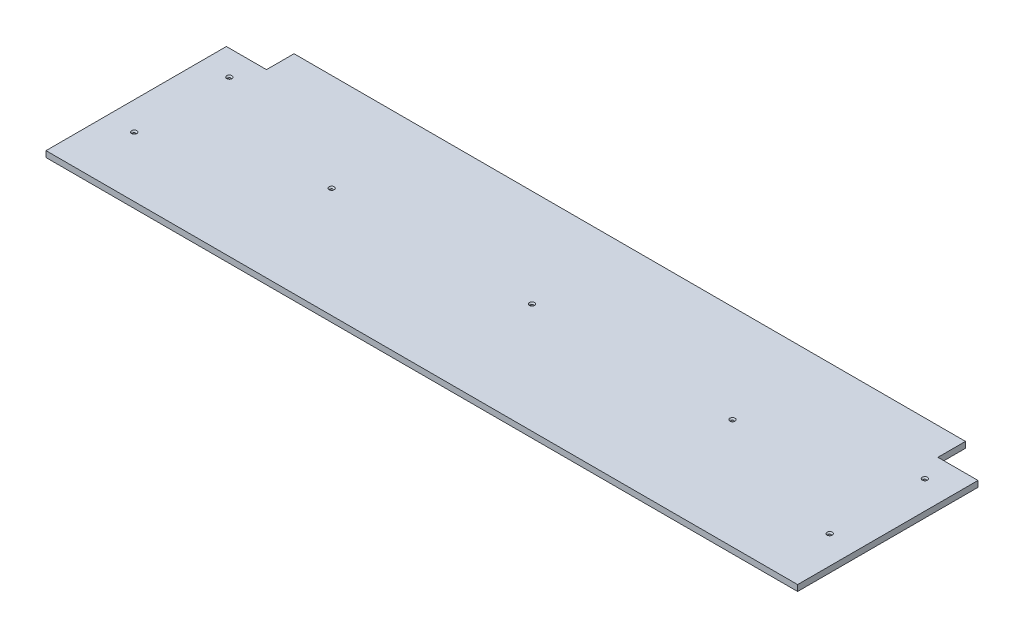
SolidWorks part; units mm, degrees
material "Balsa"
ref_plane "Front Plane" through (0, 0, 0) normal (0, 0, 1) x (1, 0, 0)
ref_plane "Top Plane" through (0, 0, 0) normal (0, 1, 0) x (1, 0, 0)
ref_plane "Right Plane" through (0, 0, 0) normal (1, 0, 0) x (0, 0, -1)
sketch "Sketch1" plane through (0, 0, 0) normal (0, 1, 0) x (1, 0, 0)
  line L1 (750, -207.5) -> (-750, -207.5)
  line L2 (750, -207.5) -> (750, 207.5)
  line L3 (750, 207.5) -> (-750, 207.5)
  line L4 (-750, -207.5) -> (-750, 207.5)
  line L5 (750, -207.5) -> (-750, 207.5) construction
  line L6 (750, 207.5) -> (-750, -207.5) construction
  point P0 (0, 0)
  dimension "D1" = 1500
  dimension "D2" = 415
extrude "RawMaterial" add sketch "Sketch1" along normal blind 12
hole_wizard "CSK for M5 Flat Head Machine Screw1" positions "Sketch3" profile "Sketch4" countersink size "M5" standard "ANSI Metric" end condition through all
sketch "Sketch3" plane through (0, 12, 0) normal (0, -1, 0) x (-1, 0, 0)
  line L6 (-750, -207.5) -> (-750, 207.5) construction
  line L7 (-750, 207.5) -> (750, 207.5) construction
  point P0 (-694, 102.5)
  point P2 (-694, -87.5)
  point P4 (-400, 12.5)
  point P6 (400, 12.5)
  point P8 (694, -87.5)
  point P10 (694, 102.5)
  point P50 (0, 12.5)
  dimension "D1" = 190
  dimension "D2" = 295
  dimension "D3" = 100
  dimension "D4" = 800
  dimension "D5" = 350
  dimension "D6" = 56
  dimension "D7" = 1444
sketch "Sketch4" plane through (694, 12, -102.5) normal (1, 0, 0) x (0, 0, 1)
  line L0 (0, 0) -> (0, 12)
  line L1 (0, 12) -> (2.6, 12)
  line L2 (2.6, 12) -> (2.6, 2.6)
  line L3 (2.6, 2.6) -> (5.2, 0)
  line L5 (5.2, 0) -> (0, 0)
  line L6 (-2.6, 2.6) -> (-5.2, 0) construction
  line L11 (0, -6.35) -> (0, 107.95) construction
  dimension "Thru Hole Dia." = 5.2
  dimension "Thru Hole Depth" = 12
  dimension "Near C'Sink Dia." = 10.4
  dimension "Near C'Sink Angle" = 90
sketch "Sketch5" plane through (0, 0, 0) normal (0, -1, 0) x (1, 0, 0)
  line L0 (-750, -152.5) -> (-670, -152.5)
  line L1 (-750, -207.5) -> (-750, 207.5) construction
  line L2 (670, -152.5) -> (670, -207.5)
  line L4 (750, -152.5) -> (670, -152.5)
  line L5 (750, 207.5) -> (750, -207.5) construction
  line L6 (750, -207.5) -> (-750, -207.5) construction
  line L7 (-670, -152.5) -> (-670, -207.5)
  line M10 (-750, 207.5) -> (-750, -207.5)
  line M11 (-750, -207.5) -> (750, -207.5)
  line M12 (750, -207.5) -> (750, 207.5)
  dimension "D1" = 80
  dimension "D2" = 55
extrude "Frame Slots" cut sketch "Sketch5" against normal through all contours L7 L0 M10 M11 | L4 L2 M12 M11 region at (710, 0, -180) region at (-710, 0, -180)
